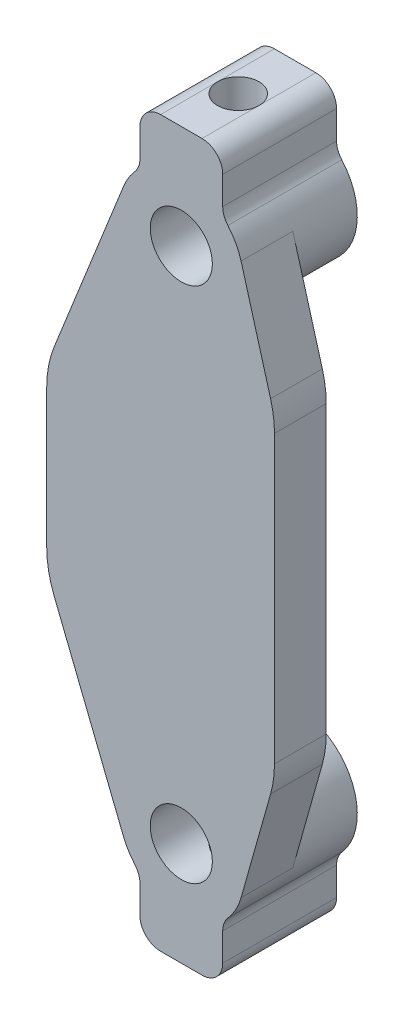
SolidWorks part; units mm, degrees
ref_plane "Front Plane" through (0, 0, 0) normal (0, 0, 1) x (1, 0, 0)
ref_plane "Top Plane" through (0, 0, 0) normal (0, 1, 0) x (1, 0, 0)
ref_plane "Right Plane" through (0, 0, 0) normal (1, 0, 0) x (0, 0, -1)
sketch "Sketch1" plane through (0, 0, 0) normal (0, 0, 1) x (1, 0, 0)
  line L0 (0, 0) -> (23, 0) construction
  line L10 (-5.5718, 27.2259) -> (-12.2864, 10.4179)
  line L11 (-13, 6.7081) -> (-13, -6.7081)
  line L16 (5.7742, 26.6304) -> (8.6237, 16.5383)
  line L17 (9, 13.821) -> (9, -13.821)
  line L19 (-5.5718, -27.2259) -> (-12.2864, -10.4179)
  line L21 (5.7742, -26.6304) -> (8.6237, -16.5383)
  line L22 (-4, -29.4721) -> (-4, -35)
  line L23 (-4, -35) -> (4, -35)
  line L24 (4, -35) -> (4, -29.4721)
  line L26 (0, -35) -> (0, -28) construction
  line L28 (4, 35) -> (4, 29.4721)
  line L29 (-4, 35) -> (4, 35)
  line L30 (-4, 29.4721) -> (-4, 35)
  circle A14 centre (0, 25) radius 3
  circle A15 centre (0, -25) radius 3
  arc A16 (-4, 29.4721) -> (4, 29.4721) centre (0, 25) ccw
  arc A17 (4, -29.4721) -> (-4, -29.4721) centre (0, -25) ccw
  arc A18 (-12.2864, 10.4179) -> (-13, 6.7081) centre (-3, 6.7081) ccw
  arc A19 (8.6237, 16.5383) -> (9, 13.821) centre (-1, 13.821) cw
  arc A20 (-12.2864, -10.4179) -> (-13, -6.7081) centre (-3, -6.7081) cw
  arc A21 (8.6237, -16.5383) -> (9, -13.821) centre (-1, -13.821) ccw
  circle A22 centre (0, -25) radius 6 construction
  circle A23 centre (0, 25) radius 6 construction
  point P13 (-13, 0)
  point P21 (9, 0)
  point P25 (0, -35)
  dimension "D2" = 10
  dimension "D3" = 22
  dimension "D10" = 6
  dimension "D4" = 50
  dimension "D5" = 9
  dimension "D7" = 8
  dimension "D6" = 7
  dimension "D11" = 3
extrude "Boss-Extrude1" add sketch "Sketch1" along normal blind 5 contours A17 A16 | A16 | A16 A14 | A16 | A16 | A16 | A17 | A17 A15 | A17 | A17 | A17 region at (-1.4758, 0, 0) region at (-4.7521, 28.3253, 0) region at (-0.304, -19.208, 0)
extrude "Boss-Extrude2" add sketch "Sketch1<8>" against normal blind 6 contours A17 A15 | A16 A14 region at (-4.7521, 28.3253, 0) region at (-0.304, -19.208, 0)
sketch "Sketch1<8>" plane through (0, 0, 0) normal (0, 0, 1) x (1, 0, 0) same geometry as "Sketch1"
fillet "Fillet1" radius 2 8 edges at (-4, 35, -0.5) (-4, 29.4721, -0.5) (4, 35, -0.5) (4, 29.4721, -0.5) (4, -29.4721, -0.5) (4, -35, -0.5) (-4, -35, -0.5) (-4, -29.4721, -0.5)
sketch "Sketch2" plane through (0, -35, 0) normal (0, -1, 0) x (1, 0, 0)
  line L0 (-2, 5) -> (2, 5) construction
  line L1 (-2, 5) -> (-2, -6) construction
  line L2 (-2, 5) -> (-2, -6)
  line L3 (-2, 5) -> (2, 5)
  circle A0 centre (0, -0.5) radius 2
  point P2 (0, 0)
  point P6 (0, 5)
  point P7 (-2, -0.5)
  dimension "D1" = 4
extrude "Cut-Extrude1" cut sketch "Sketch2" against normal up to next contours A0 region at (0, -35, -0.5)
extrude "Cut-Extrude2" cut sketch "Sketch2<3>" along normal up to next from surface contours A0 region at (0, -35, -0.5) starting at face at (0, 35, -0.5)
sketch "Sketch2<3>" plane through (0, -35, 0) normal (0, -1, 0) x (1, 0, 0) same geometry as "Sketch2"
equation "\"in_d\"=40"
equation "\"pipe_thick\"=2"
equation "\"rod_angle\"=20"
equation "\"rod_radius\"=33.5"
equation "\"rod_diameter\"=8"
equation "\"lin_bear_h\"=24"
equation "\"screw_radius\"=40"
equation "\"screw_angle\"=50"
equation "\"lin_bearing_d\"=15"
equation "\"drill_rod_pair\"=37"
equation "\"support_rod_w\"=50"
equation "\"vertical_slider_w\"=65"
equation "\"slope_angle\"=30"
